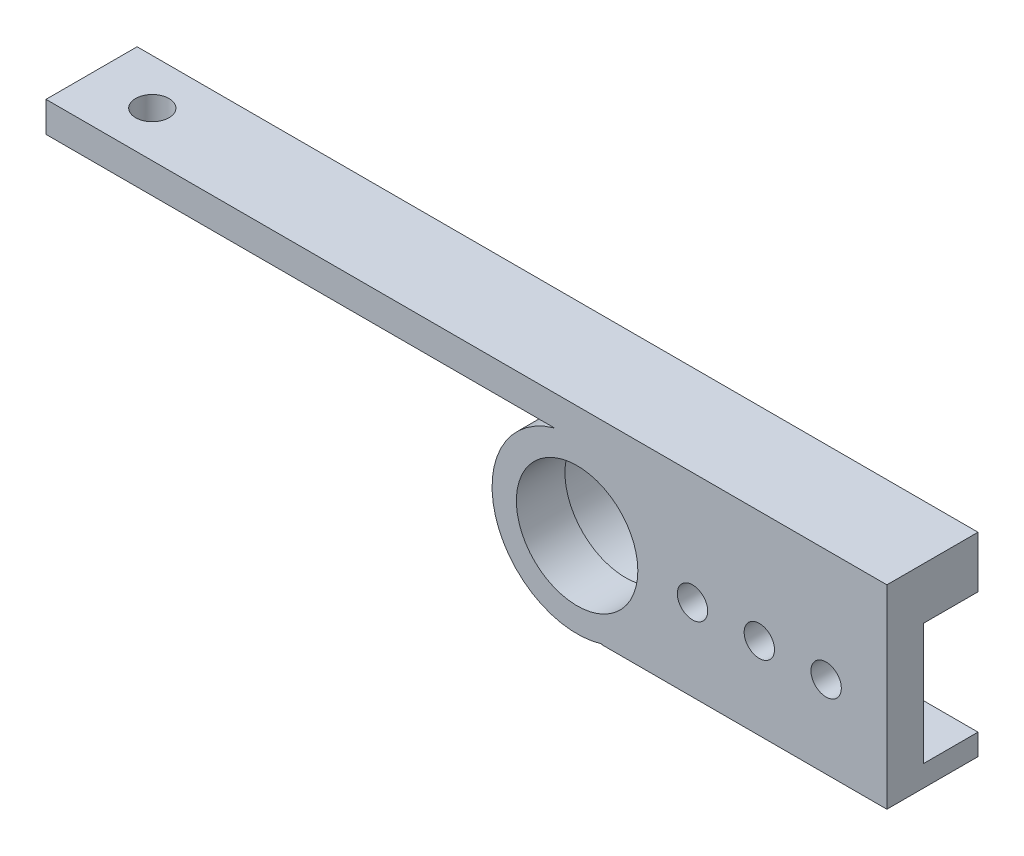
SolidWorks part; units mm, degrees
ref_plane "前视基准面" through (0, 0, 0) normal (0, 0, 1) x (1, 0, 0)
ref_plane "上视基准面" through (0, 0, 0) normal (0, 1, 0) x (1, 0, 0)
ref_plane "右视基准面" through (0, 0, 0) normal (1, 0, 0) x (0, 0, -1)
sketch "草图1" plane through (0, 0, 0) normal (0, 0, 1) x (1, 0, 0)
  line L1 (20, -10) -> (-20, -10)
  line L2 (20, -10) -> (20, 10)
  line L3 (20, 10) -> (-20, 10)
  line L4 (-20, -10) -> (-20, 10)
  line L5 (20, -10) -> (-20, 10) construction
  line L6 (20, 10) -> (-20, -10) construction
  point P0 (0, 0)
  dimension "D1" = 40
  dimension "D2" = 20
extrude "凸台-拉伸1" add sketch "草图1" along normal blind 6
sketch "草图2" plane through (0, 0, 6) normal (0, 0, 1) x (1, 0, 0)
  line L0 (20, -10) -> (20, 10) construction
  circle A0 centre (10, 0) radius 2.5
  circle A1 centre (-1, 0) radius 2.5
  circle A2 centre (-12, 0) radius 2.5
  dimension "D1" = 10
  dimension "D2" = 5
  dimension "D3" = 3
extrude "切除-拉伸1" cut sketch "草图2" against normal through all
sketch "草图3" plane through (0, 0, 6) normal (0, 0, 1) x (1, 0, 0)
  line L0 (20, 13.5) -> (20, 10)
  line L1 (20, -13.5) -> (-26.894, -13.5)
  line L3 (20, 13.5) -> (-26.894, 13.5)
  line L4 (-20, 10) -> (-20, -10)
  line L5 (-20, -10) -> (20, -10)
  line L6 (20, -10) -> (20, 10)
  line L7 (20, 10) -> (-20, 10)
  line L8 (-20, 10) -> (-20, -10)
  line L9 (-20, -10) -> (20, -10)
  line L10 (20, -10) -> (20, 10)
  line L11 (20, 10) -> (-20, 10)
  line L12 (-26.894, -13.5) -> (-26.894, 13.5)
  line L13 (20, -10.0394) -> (-26.894, 13.5) construction
  line L14 (20, 10.0394) -> (-26.894, -13.5) construction
  line L15 (20, -10) -> (20, -13.5)
  circle A0 centre (-31, 0) radius 11
  circle A1 centre (-31, 0) radius 14
  point P2 (0, 0)
  line M10 (-20, 10) -> (-20, -10)
  line M11 (-20, -10) -> (20, -10)
  line M13 (20, 10) -> (-20, 10)
  dimension "D3" = 22
  dimension "D4" = 28
  dimension "D2" = 3.5
  dimension "D1" = 0
extrude "凸台-拉伸2" add sketch "草图3" against normal blind 15 contours L3 A1 L1 L12 A0 | A1 L1 L15 M11 M10 | L1 A1 L8 A0 L12 | L8 A1 L3 L12 A0 | L8 A1 | A1 L0 L3 M10 M13 region at (-1.9449, 11.7771, 6) region at (-1.9449, -11.7771, 6) region at (-23.0173, 9.0328, 6) region at (-27.2274, 11.7946, 6) region at (-18.7882, 0, 6) region at (-23.0173, -9.0328, 6)
sketch "草图5" plane through (0, 0, 6) normal (0, 0, 1) x (1, 0, 0)
  circle A0 centre (-31, 0) radius 10
  circle A1 centre (-31, 0) radius 11 construction
  circle A2 centre (-31, 0) radius 11
  dimension "D1" = 20
extrude "凸台-拉伸3" add sketch "草图5" against normal blind 8
sketch "草图6" plane through (0, 0, 6) normal (0, 0, 1) x (1, 0, 0)
  circle A0 centre (-31, 0) radius 8.5
  circle A1 centre (-31, 0) radius 10 construction
  circle A2 centre (-31, 0) radius 10
  dimension "D1" = 17
sketch "草图7" plane through (0, 13.5, 0) normal (0, 1, 0) x (1, 0, 0)
  circle A0 centre (-16.8213, 3.0525) radius 3.3366
sketch "草图8" plane through (20, 0, 0) normal (1, 0, 0) x (0, 0, -1)
  line L1 (-6, 13.5) -> (9, 13.5)
  line L2 (-6, 13.5) -> (-6, 18.5)
  line L3 (-6, 18.5) -> (9, 18.5)
  line L4 (9, 13.5) -> (9, 18.5)
  dimension "D1" = 5
extrude "凸台-拉伸4" add sketch "草图8" against normal blind 200
sketch "草图9" plane through (0, 0, 6) normal (0, 0, 1) x (1, 0, 0)
  line L1 (-29.5663, 15.6648) -> (-25.1627, 15.6648)
  line L2 (-29.5663, 15.6648) -> (-29.5663, 11.9284)
  line L3 (-29.5663, 11.9284) -> (-25.1627, 11.9284)
  line L4 (-25.1627, 15.6648) -> (-25.1627, 11.9284)
extrude "凸台-拉伸5" add sketch "草图9" against normal through all
sketch "草图11" plane through (0, 18.5, 0) normal (0, 1, 0) x (1, 0, 0)
  line L0 (-118.4338, -6) -> (-118.4338, 9)
  line L1 (-180, -6) -> (20, -6) construction
  line L2 (-118.4338, 241.5018) -> (-118.4338, -128.4982) construction
  line L3 (-180, 9) -> (20, 9) construction
sketch "草图13" plane through (0, 18.5, 0) normal (0, 1, 0) x (1, 0, 0)
  line L1 (-118.4338, -6) -> (-183.1111, -6)
  line L2 (-118.4338, -6) -> (-118.4338, 12.5245)
  line L3 (-118.4338, 12.5245) -> (-183.1111, 12.5245)
  line L4 (-183.1111, -6) -> (-183.1111, 12.5245)
extrude "切除-拉伸2" cut sketch "草图13" against normal through all
sketch "草图14" plane through (0, 18.5, 0) normal (0, 1, 0) x (1, 0, 0)
  line L0 (-118.4338, 1.5) -> (-108.4338, 1.5)
  line L1 (-118.4338, -6) -> (-118.4338, 9) construction
  circle A0 centre (-108.4338, 1.5) radius 2.75
  dimension "D2" = 5.5
  dimension "D1" = 10
extrude "切除-拉伸3" cut sketch "草图14" against normal blind 10 contours A0
